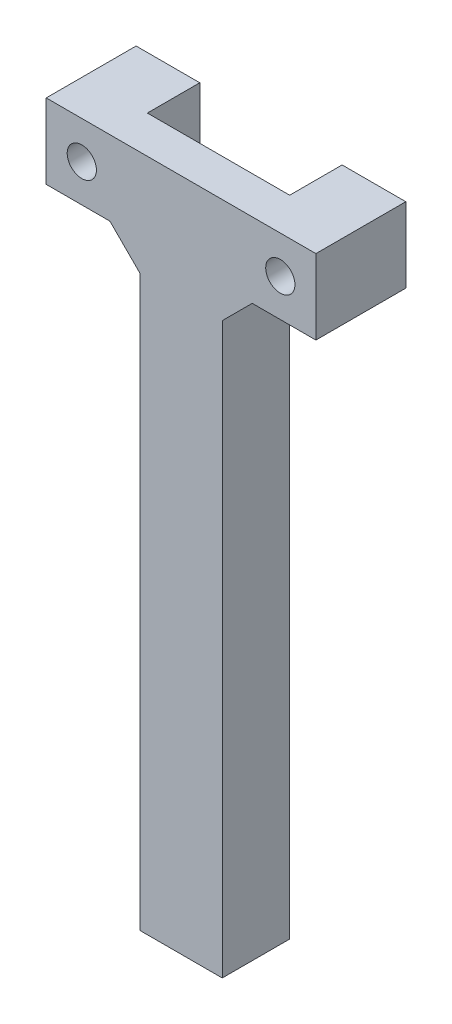
SolidWorks part; units mm, degrees
ref_plane "Front Plane" through (0, 0, 0) normal (0, 0, 1) x (1, 0, 0)
ref_plane "Top Plane" through (0, 0, 0) normal (0, 1, 0) x (1, 0, 0)
ref_plane "Right Plane" through (0, 0, 0) normal (1, 0, 0) x (0, 0, -1)
sketch "Sketch1" plane through (0, 0, 0) normal (0, 1, 0) x (1, 0, 0)
  line L1 (-5.5, 0) -> (5.5, 0)
  line L2 (-5.5, 0) -> (-5.5, -9)
  line L3 (-5.5, -9) -> (5.5, -9)
  line L4 (5.5, 0) -> (5.5, -9)
  line L5 (0, -9) -> (0, 0) construction
  line L6 (-5.5, -4.5) -> (5.5, -4.5) construction
  point P4 (0, 0)
  point P92 (0, -4.5)
  dimension "D1" = 11
  dimension "D2" = 9
extrude "Boss-Extrude1" add sketch "Sketch1" against normal blind 80
sketch "Sketch2" plane through (0, 0, 0) normal (0, 1, 0) x (1, 0, 0)
  line L0 (-13.25, 3) -> (13.25, 3) construction
  line L1 (-9.5, 3) -> (-9.5, -4)
  line L2 (-9.5, -4) -> (9.5, -4)
  line L3 (9.5, -4) -> (9.5, 3)
  line L4 (9.5, 3) -> (18, 3)
  line L5 (18, 3) -> (18, -9)
  line L6 (18, -9) -> (-18, -9)
  line L7 (-18, -9) -> (-18, 3)
  line L8 (-18, 3) -> (-9.5, 3)
  line L9 (-5.5, -9) -> (5.5, -9) construction
  line L10 (0, 0) -> (0, -4) construction
  line L11 (5.5, 0) -> (-5.5, 0) construction
  point P15 (0, 0)
  dimension "D1" = 26.5
  dimension "D2" = 19
  dimension "D3" = 7
  dimension "D4" = 36
  dimension "D5" = 4
extrude "Boss-Extrude2" add sketch "Sketch2" along normal blind 10
hole_wizard "Ø3.9 (3.9) Diameter Hole1" positions "Sketch3" profile "Sketch4" hole size "Ø3.9" standard "ANSI Metric" end condition up to next
sketch "Sketch3" plane through (0, 0, -3) normal (0, 0, -1) x (-1, 0, 0)
  line L0 (-13.25, 5) -> (13.25, 5) construction
  line L1 (13.25, 5) -> (18, 5) construction
  line L2 (18, 10) -> (18, 0) construction
  line L5 (0, 5) -> (0, 0) construction
  point P0 (-13.25, 5)
  point P2 (13.25, 5)
  point P25 (12.3081, 0)
  dimension "D1" = 26.5
sketch "Sketch4" plane through (13.25, 5, -3) normal (1, 0, 0) x (0, 1, 0)
  line L0 (0, 0) -> (0, 12)
  line L1 (0, 12) -> (1.95, 12)
  line L2 (1.95, 12) -> (1.95, 0)
  line L5 (1.95, 0) -> (0, 0)
  line L11 (0, -6.35) -> (0, 107.95) construction
  dimension "Thru Hole Dia." = 3.9
  dimension "Thru Hole Depth" = 12
chamfer "Chamfer1" distance 4 angle 45 3 edges at (0, 0, 0) (-5.5, 0, 6.5) (5.5, 0, 6.5)
hole_wizard "M6x1.0 Tapped Hole1" positions "Sketch5" profile "Sketch6" tap size "M6x1.0" standard "ANSI Metric"
sketch "Sketch5" plane through (0, -80, 0) normal (0, -1, 0) x (-1, 0, 0)
  line L0 (0, -4.5) -> (0, -9) construction
  line L1 (5.5, -9) -> (-5.5, -9) construction
  point P1 (0, -4.5)
  dimension "D1" = 4.5
sketch "Sketch6" plane through (0, -80, 4.5) normal (1, 0, 0) x (0, 0, -1)
  line L0 (0, 0) -> (0, 16.5022)
  line L1 (0, 16.5022) -> (2.5, 15)
  line L2 (2.5, 15) -> (2.5, 0)
  line L5 (2.5, 0) -> (0, 0)
  line L10 (0, 16.5022) -> (-2.5, 15) construction
  line L11 (0, -6.35) -> (0, 107.95) construction
  dimension "Tap Drill Dia." = 5
  dimension "Tap Drill Depth" = 15
  dimension "Drill Angle" = 118
cosmetic thread "Hole Thread1" parameters "D1"=12, "D2"=6
